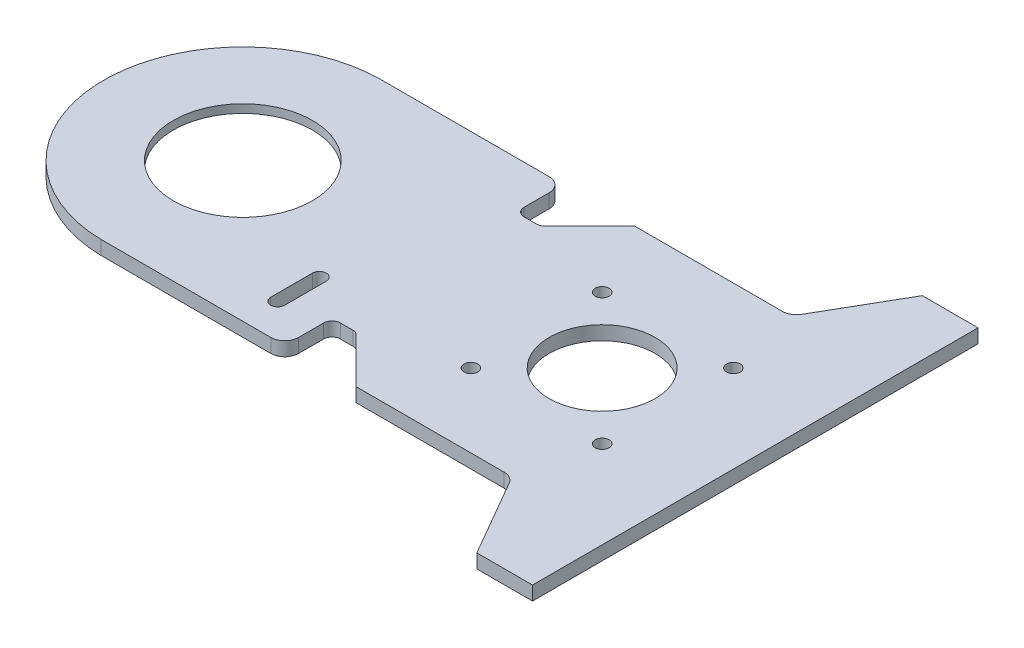
SolidWorks part; units mm, degrees
ref_plane "Front Plane" through (0, 0, 0) normal (0, 0, 1) x (1, 0, 0)
ref_plane "Top Plane" through (0, 0, 0) normal (0, 1, 0) x (1, 0, 0)
ref_plane "Right Plane" through (0, 0, 0) normal (1, 0, 0) x (0, 0, -1)
sketch "Sketch1" plane through (0, 0, 0) normal (0, 1, 0) x (1, 0, 0)
  line L0 (15.2546, 44.9902) -> (15.2546, 35.9902)
  line L1 (-50.7454, -49.9902) -> (10.2546, -49.9902)
  line L3 (-50.7454, 49.9902) -> (10.2546, 49.9902)
  line L5 (-50.7454, -49.9902) -> (50.7454, 49.9902) construction
  line L6 (-50.7454, 49.9902) -> (50.7454, -49.9902) construction
  line L7 (18.2546, 32.9902) -> (22.7119, 32.9902)
  line L8 (24.8333, 33.8689) -> (40.9546, 49.9902)
  line L9 (40.9546, 49.9902) -> (94.0678, 49.9902)
  line L10 (98.398, 52.4902) -> (114.2807, 80)
  line L11 (114.2807, 80) -> (134.2807, 80)
  line L12 (-49.7577, 0) -> (134.2807, 0) construction
  line L13 (134.2807, 80) -> (134.2807, -80)
  line L14 (40.9546, 49.9902) -> (96.9546, 49.9902)
  line L15 (40.9546, 49.9902) -> (50.7454, 49.9902)
  line L17 (114.2807, -80) -> (134.2807, -80)
  line L18 (98.398, -52.4902) -> (114.2807, -80)
  line L19 (40.9546, -49.9902) -> (94.0678, -49.9902)
  line L20 (18.2546, -32.9902) -> (22.7119, -32.9902)
  line L21 (24.8333, -33.8689) -> (40.9546, -49.9902)
  line L22 (15.2546, -44.9902) -> (15.2546, -35.9902)
  line L23 (40.9546, -49.9902) -> (50.7454, -49.9902)
  arc A0 (-50.7454, 49.9902) -> (-50.7454, -49.9902) centre (-49.7577, 0) ccw
  arc A1 (22.7119, 32.9902) -> (24.8333, 33.8689) centre (22.7119, 35.9902) ccw
  arc A2 (18.2546, 32.9902) -> (15.2546, 35.9902) centre (18.2546, 35.9902) cw
  arc A3 (15.2546, 44.9902) -> (10.2546, 49.9902) centre (10.2546, 44.9902) ccw
  arc A4 (15.2546, -44.9902) -> (10.2546, -49.9902) centre (10.2546, -44.9902) cw
  arc A5 (22.7119, -32.9902) -> (24.8333, -33.8689) centre (22.7119, -35.9902) cw
  arc A6 (18.2546, -32.9902) -> (15.2546, -35.9902) centre (18.2546, -35.9902) ccw
  arc A7 (98.398, -52.4902) -> (94.0678, -49.9902) centre (94.0678, -54.9902) ccw
  arc A8 (98.398, 52.4902) -> (94.0678, 49.9902) centre (94.0678, 54.9902) cw
  point P0 (0, 0)
  point P24 (23.9546, 32.9902)
  point P27 (15.2546, 32.9902)
  point P30 (15.2546, 49.9902)
  point P33 (15.2546, -49.9902)
  point P37 (23.9546, -32.9902)
  point P40 (15.2546, -32.9902)
  point P43 (96.9546, -49.9902)
  dimension "D2" = 100
  dimension "D11" = 3
  dimension "D12" = 5
  dimension "D13" = 5
  dimension "D14" = 3
  dimension "D15" = 5
  dimension "D1" = 120
  dimension "D3" = 8.7
  dimension "D4" = 135
  dimension "D5" = 17
  dimension "D6" = 56
  dimension "D7" = 160
  dimension "D8" = 20
  dimension "D10" = 66
extrude "Boss-Extrude1" add sketch "Sketch1" along normal blind 5 contours L3 A0 L1 L13 L11 L10 L14 L9 L8 L7 L0 region at (29.4264, 0, 0)
sketch "Sketch4" plane through (0, 5, 0) normal (0, 1, 0) x (1, 0, 0)
  line L0 (22.7119, 32.9902) -> (22.7119, -32.9902) construction
  line L1 (22.7119, 0) -> (-0.2253, 0) construction
  line L2 (22.7119, 21) -> (13.7119, 21)
  line L3 (10.7119, 18) -> (10.7119, -18)
  line L4 (13.7119, -21) -> (22.7119, -21)
  line L5 (10.7119, 21) -> (22.7119, -21) construction
  line L6 (22.7119, 21) -> (10.7119, -21) construction
  line L7 (22.7119, 21) -> (22.7119, -21)
  arc A0 (13.7119, -21) -> (10.7119, -18) centre (13.7119, -18) cw
  arc A1 (10.7119, 18) -> (13.7119, 21) centre (13.7119, 18) cw
  point P8 (16.7119, 0)
  dimension "D3" = 3
  dimension "D1" = 42
  dimension "D2" = 12
extrude "Cut-Extrude2" [suppressed] cut sketch "Sketch4" against normal through all
sketch "Sketch10" plane through (0, 5, 0) normal (0, 1, 0) x (1, 0, 0)
  line L0 (-99.7577, 0) -> (134.2807, 0) construction
  line L1 (134.2807, 28.2) -> (134.2807, -28.2)
  line L2 (102.8507, -23.57) -> (55.7107, -23.57) construction
  line L3 (102.8507, -23.57) -> (102.8507, 23.57) construction
  line L4 (102.8507, 23.57) -> (55.7107, 23.57) construction
  line L5 (55.7107, -23.57) -> (55.7107, 23.57) construction
  line L6 (102.8507, -23.57) -> (55.7107, 23.57) construction
  line L7 (102.8507, 23.57) -> (55.7107, -23.57) construction
  circle A0 centre (79.2807, 0) radius 19.05
  circle A1 centre (55.7107, 23.57) radius 2.5
  circle A2 centre (102.8507, 23.57) radius 2.5
  circle A3 centre (102.8507, -23.57) radius 2.5
  circle A4 centre (55.7107, -23.57) radius 2.5
  circle A8 centre (-49.7577, 0) radius 25
  arc A9 (-50.2516, 24.9951) -> (-50.2516, -24.9951) centre (-49.7577, 0) ccw
  arc A10 (-50.2516, 24.9951) -> (-50.2516, -24.9951) centre (-49.7577, 0) ccw
  point P6 (79.2807, 0)
  point P7 (134.2807, 0)
  dimension "D2" = 38.1
  dimension "D5" = 5
  dimension "D7" = 25
  dimension "D8" = 50
  dimension "D1" = 56.4
  dimension "D3" = 47.14
  dimension "D4" = 47.14
  dimension "D6" = 55
extrude "Cut-Extrude7" cut sketch "Sketch10" against normal through all contours A1 | A0 | A4 | A2 | A3 | A8 region at (79.2807, 5, 0) region at (55.7107, 5, -23.57) region at (102.8507, 5, -23.57) region at (102.8507, 5, 23.57) region at (55.7107, 5, 23.57)
sketch "Sketch11" plane through (0, 0, 0) normal (0, -1, 0) x (1, 0, 0)
  circle A0 centre (-49.7577, 0) radius 31
  dimension "D1" = 62
extrude "Cut-Extrude8" cut sketch "Sketch11" against normal blind 2
sketch "Sketch12" plane through (0, 0, 0) normal (0, -1, 0) x (1, 0, 0)
  line L0 (-49.7577, 0) -> (134.2807, 0) construction
  line L1 (134.2807, -80) -> (134.2807, 80) construction
  line L2 (0.2423, 0) -> (0.2423, 24.4796) construction
  line L3 (-2.2577, 37.5) -> (-2.2577, 22.5)
  line L4 (2.7423, 37.5) -> (2.7423, 22.5)
  line L5 (2.7423, 22.5) -> (2.7423, 37.5)
  arc A0 (2.7423, 37.5) -> (-2.2577, 37.5) centre (0.2423, 37.5) ccw
  arc A1 (-2.2577, 22.5) -> (2.7423, 22.5) centre (0.2423, 22.5) ccw
  point P16 (0, 0)
  point P17 (-2.2577, 30)
  dimension "D2" = 15
  dimension "D4" = 5
  dimension "D1" = 50
  dimension "D3" = 30
extrude "Cut-Extrude9" cut sketch "Sketch12" against normal through all contours L3 A1 L4 A0 region at (0.2423, 0, 30)
